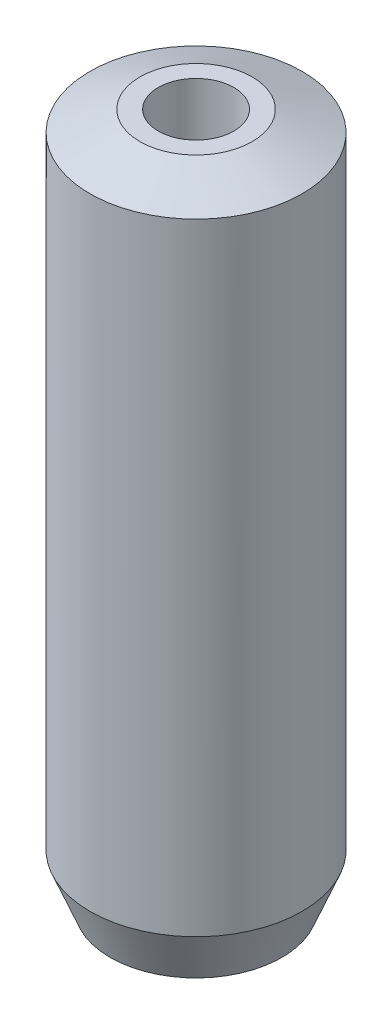
SolidWorks part; units mm, degrees
ref_plane "Front Plane" through (0, 0, 0) normal (0, 0, 1) x (1, 0, 0)
ref_plane "Top Plane" through (0, 0, 0) normal (0, 1, 0) x (1, 0, 0)
ref_plane "Right Plane" through (0, 0, 0) normal (1, 0, 0) x (0, 0, -1)
sketch "Sketch1" plane through (0, 0, 0) normal (0, 1, 0) x (1, 0, 0)
  circle A0 centre (0, 0) radius 30
  dimension "SHAFT_OD" = 60
extrude "Boss-Extrude1" add sketch "Sketch1" along normal blind 195.6019
sketch "Sketch2" plane through (0, 0, 0) normal (0, 1, 0) x (1, 0, 0)
  circle A0 centre (0, 0) radius 10.6924
  dimension "BORE_D" = 21.3848
extrude "Cut-Extrude1" cut sketch "Sketch2" along normal through all
chamfer "Chamfer1" distance 5.7024 angle 68.033 2 edges at (0, 195.6019, 30) (0, 0, 30) first distance on face at (0, 195.6019, 30) first distance on face at (0, 0, 10.6924)
